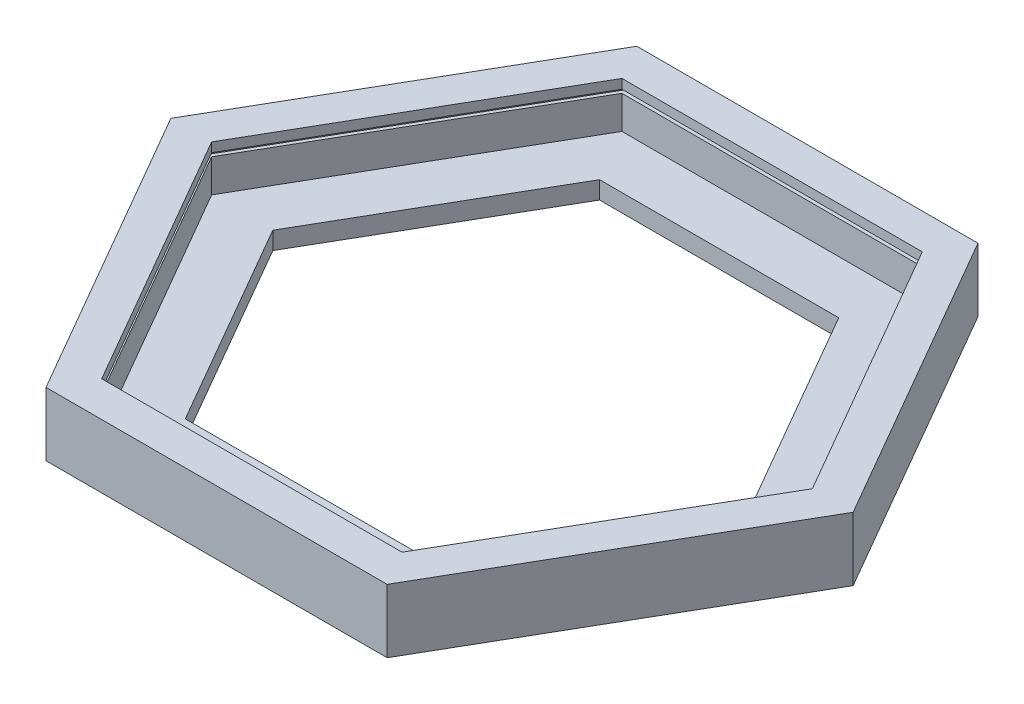
SolidWorks part; units mm, degrees
ref_plane "Front Plane" through (0, 0, 0) normal (0, 0, 1) x (1, 0, 0)
ref_plane "Top Plane" through (0, 0, 0) normal (0, 1, 0) x (1, 0, 0)
ref_plane "Right Plane" through (0, 0, 0) normal (1, 0, 0) x (0, 0, -1)
sketch "Profiles Sketch" plane through (0, 0, 0) normal (0, 1, 0) x (1, 0, 0)
  line L1 (-42.5263, -73.6577) -> (42.5263, -73.6577)
  line L2 (42.5263, -73.6577) -> (85.0526, 0)
  line L3 (85.0526, 0) -> (42.5263, 73.6577)
  line L4 (42.5263, 73.6577) -> (-42.5263, 73.6577)
  line L5 (-42.5263, 73.6577) -> (-85.0526, 0)
  line L6 (-85.0526, 0) -> (-42.5263, -73.6577)
  line L7 (-48.2998, -83.6577) -> (48.2998, -83.6577)
  line L8 (48.2998, -83.6577) -> (96.5996, 0)
  line L9 (96.5996, 0) -> (48.2998, 83.6577)
  line L10 (48.2998, 83.6577) -> (-48.2998, 83.6577)
  line L11 (-48.2998, 83.6577) -> (-96.5996, 0)
  line L12 (-96.5996, 0) -> (-48.2998, -83.6577)
  line L13 (33.866, 58.6577) -> (-33.866, 58.6577)
  line L14 (-33.866, 58.6577) -> (-67.7321, 0)
  line L15 (-67.7321, 0) -> (-33.866, -58.6577)
  line L16 (-33.866, -58.6577) -> (33.866, -58.6577)
  line L17 (33.866, -58.6577) -> (67.7321, 0)
  line L18 (67.7321, 0) -> (33.866, 58.6577)
  circle A0 centre (0, 0) radius 85.0526 construction
  circle A1 centre (0, 0) radius 96.5996 construction
  circle A2 centre (0, 0) radius 58.6577 construction
  dimension "D1" = 85.0526
  dimension "D2" = 10
  dimension "D3" = 15
extrude "Base Hexagon" add sketch "Profiles Sketch" along normal blind 5 contours L5 L6 L1 L2 L3 L4 | L11 L12 L7 L8 L9 L10 L6 L5 L4 L3 L2 L1 region at (-61.8406, 0, 35.7037) region at (-70.2363, 0, 40.5509)
extrude "Outer Wall" add sketch "Sketch1<3>" along normal blind 18 contours L11 L12 L7 L8 L9 L10 L6 L5 L4 L3 L2 L1 region at (-70.2363, 0, 40.5509)
sketch "Sketch1<3>" plane through (0, 0, 0) normal (0, 1, 0) x (1, 0, 0) same geometry as "Profiles Sketch"
ref_plane "Fill Plane" through (0, 14.35, 0) normal (0, 1, 0) x (1, 0, 0)
sketch "Fill Line Sketch" plane through (0, 14.35, 0) normal (0, 1, 0) x (1, 0, 0)
  line L1 (85.0526, 0) -> (42.5263, 73.6577)
  line L2 (42.5263, 73.6577) -> (-42.5263, 73.6577)
  line L3 (-42.5263, 73.6577) -> (-85.0526, 0)
  line L4 (-85.0526, 0) -> (-42.5263, -73.6577)
  line L5 (-42.5263, -73.6577) -> (42.5263, -73.6577)
  line L6 (42.5263, -73.6577) -> (85.0526, 0)
  line L7 (86.2073, 0) -> (43.1036, 74.6577)
  line L8 (43.1036, 74.6577) -> (-43.1036, 74.6577)
  line L9 (-43.1036, 74.6577) -> (-86.2073, 0)
  line L10 (-86.2073, 0) -> (-43.1036, -74.6577)
  line L11 (-43.1036, -74.6577) -> (43.1036, -74.6577)
  line L12 (43.1036, -74.6577) -> (86.2073, 0)
  circle A0 centre (0, 0) radius 73.6577 construction
  circle A1 centre (0, 0) radius 74.6577 construction
  dimension "D1" = 1
extrude "Fill Line" cut sketch "Fill Line Sketch" along normal blind 1
